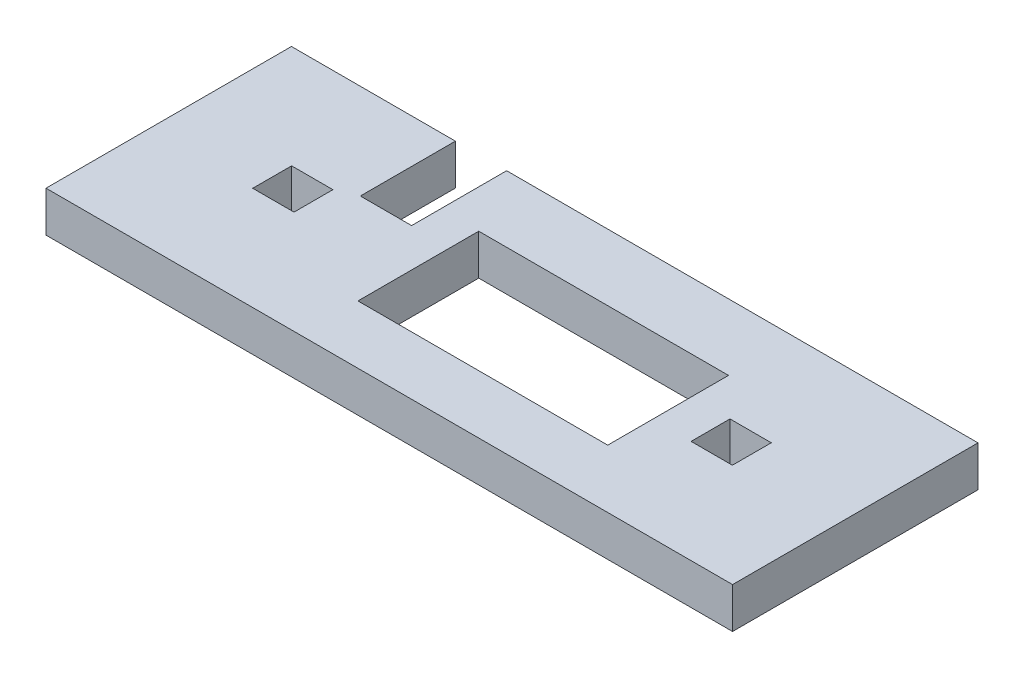
SolidWorks part; units mm, degrees
material "6061 Alloy"
ref_plane "Front Plane" through (0, 0, 0) normal (0, 0, 1) x (1, 0, 0)
ref_plane "Top Plane" through (0, 0, 0) normal (0, 1, 0) x (1, 0, 0)
ref_plane "Right Plane" through (0, 0, 0) normal (1, 0, 0) x (0, 0, -1)
sketch "Sketch1" plane through (0, 0, 0) normal (0, 1, 0) x (1, 0, 0)
  line L0 (107.2, 76.65) -> (107.2, 0) construction
  line L1 (0, 0) -> (214.4, 0)
  line L2 (0, 0) -> (0, 76.65)
  line L3 (0, 76.65) -> (214.4, 76.65)
  line L4 (214.4, 0) -> (214.4, 76.65)
  line L5 (32.3, 44.4) -> (45.2, 44.4)
  line L6 (32.3, 44.4) -> (32.3, 32.25)
  line L7 (32.3, 32.25) -> (45.2, 32.25)
  line L8 (45.2, 44.4) -> (45.2, 32.25)
  line L9 (182.1, 32.25) -> (169.2, 32.25)
  line L10 (169.2, 44.4) -> (169.2, 32.25)
  line L11 (182.1, 44.4) -> (169.2, 44.4)
  line L12 (182.1, 44.4) -> (182.1, 32.25)
  dimension "D1" = 214.4
  dimension "D2" = 76.65
  dimension "D3" = 32.25
  dimension "D4" = 32.25
  dimension "D5" = 62
  dimension "D6" = 12.9
extrude "Boss-Extrude1" add sketch "Sketch1" along normal blind 12.7
sketch "Sketch2" plane through (0, 12.7, 0) normal (0, 1, 0) x (1, 0, 0)
  line L0 (214.4, 76.65) -> (0, 76.65) construction
  line L1 (51.2, 76.65) -> (67.2, 76.65)
  line L2 (51.2, 76.65) -> (51.2, 46.9664)
  line L3 (51.2, 46.9664) -> (67.2, 46.9664)
  line L4 (67.2, 76.65) -> (67.2, 46.9664)
  line L5 (45.2, 32.25) -> (45.2, 44.4) construction
  line L6 (79.2, 55.9402) -> (157.2, 55.9402)
  line L7 (79.2, 55.9402) -> (79.2, 18.2171)
  line L8 (79.2, 18.2171) -> (157.2, 18.2171)
  line L9 (157.2, 55.9402) -> (157.2, 18.2171)
  line L10 (169.2, 44.4) -> (169.2, 32.25) construction
  dimension "D1" = 6
  dimension "D2" = 16
  dimension "D3" = 12
  dimension "D4" = 12
extrude "Cut-Extrude1" cut sketch "Sketch2" against normal through all
